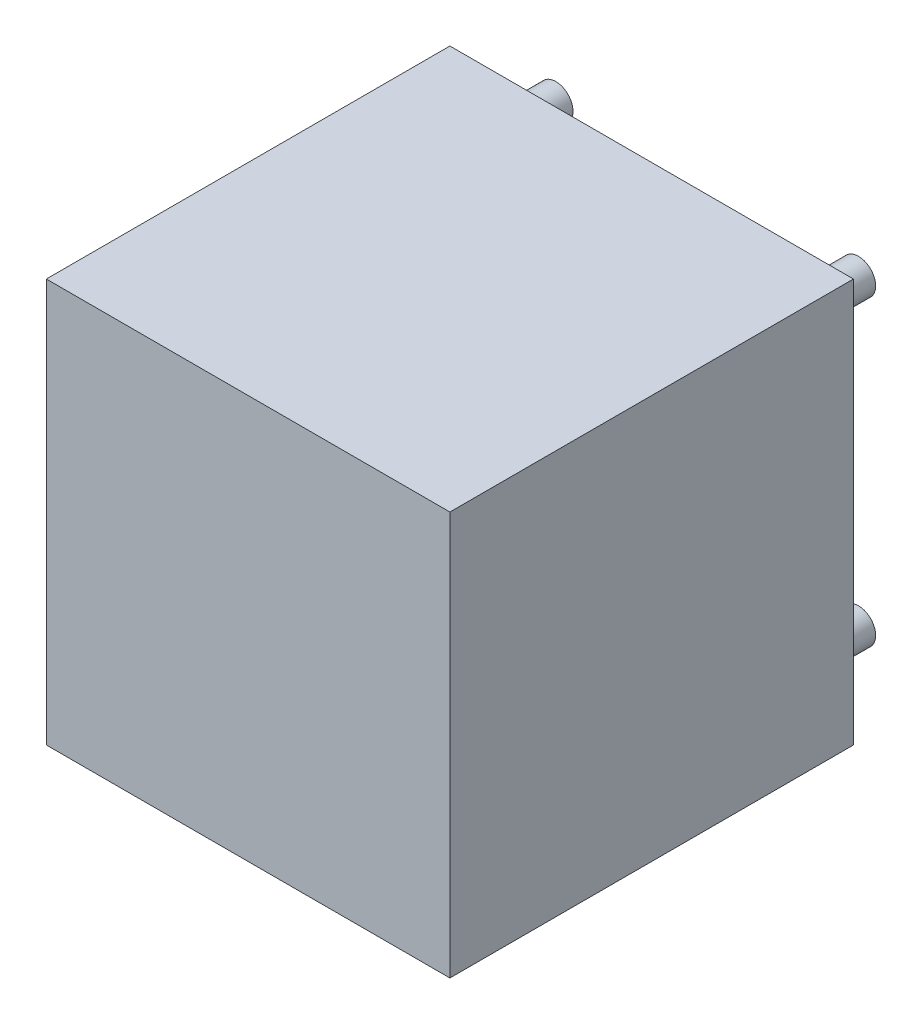
SolidWorks part; units mm, degrees
ref_plane "Front Plane" through (0, 0, 0) normal (0, 0, 1) x (1, 0, 0)
ref_plane "Top Plane" through (0, 0, 0) normal (0, 1, 0) x (1, 0, 0)
ref_plane "Right Plane" through (0, 0, 0) normal (1, 0, 0) x (0, 0, -1)
sketch "Sketch1" plane through (0, 0, 0) normal (0, 0, 1) x (1, 0, 0)
  line L1 (-20, -20) -> (20, -20)
  line L2 (-20, -20) -> (-20, 20)
  line L3 (-20, 20) -> (20, 20)
  line L4 (20, -20) -> (20, 20)
  line L5 (-20, -20) -> (20, 20) construction
  line L6 (-20, 20) -> (20, -20) construction
  point P0 (0, 0)
  dimension "D1" = 40
  dimension "D2" = 40
extrude "Boss-Extrude1" add sketch "Sketch1" along normal blind 40
sketch "Sketch2" plane through (0, 0, 0) normal (0, 0, -1) x (-1, 0, 0)
  line L0 (20, 20) -> (20, -20) construction
  line L2 (20, -20) -> (-20, -20) construction
  circle A0 centre (15, -15) radius 1.7
  dimension "D3" = 3.4
  dimension "D1" = 5
  dimension "D2" = 5
extrude "Boss-Extrude2" add sketch "Sketch2" along normal blind 5.5
mirror "Mirror1" about plane through (0, 0, 0) normal (1, 0, 0) of "Boss-Extrude2"
mirror "Mirror2" about plane through (0, 0, 0) normal (0, 1, 0) of "Mirror1"
sketch "Sketch3" plane through (0, 0, 0) normal (0, 0, -1) x (-1, 0, 0)
  circle A0 centre (0, 0) radius 2.5
  dimension "D1" = 5
extrude "Boss-Extrude3" add sketch "Sketch3" along normal blind 10
equation "\"D1@Boss-Extrude2\" = \"mat@V1.assembly\""
